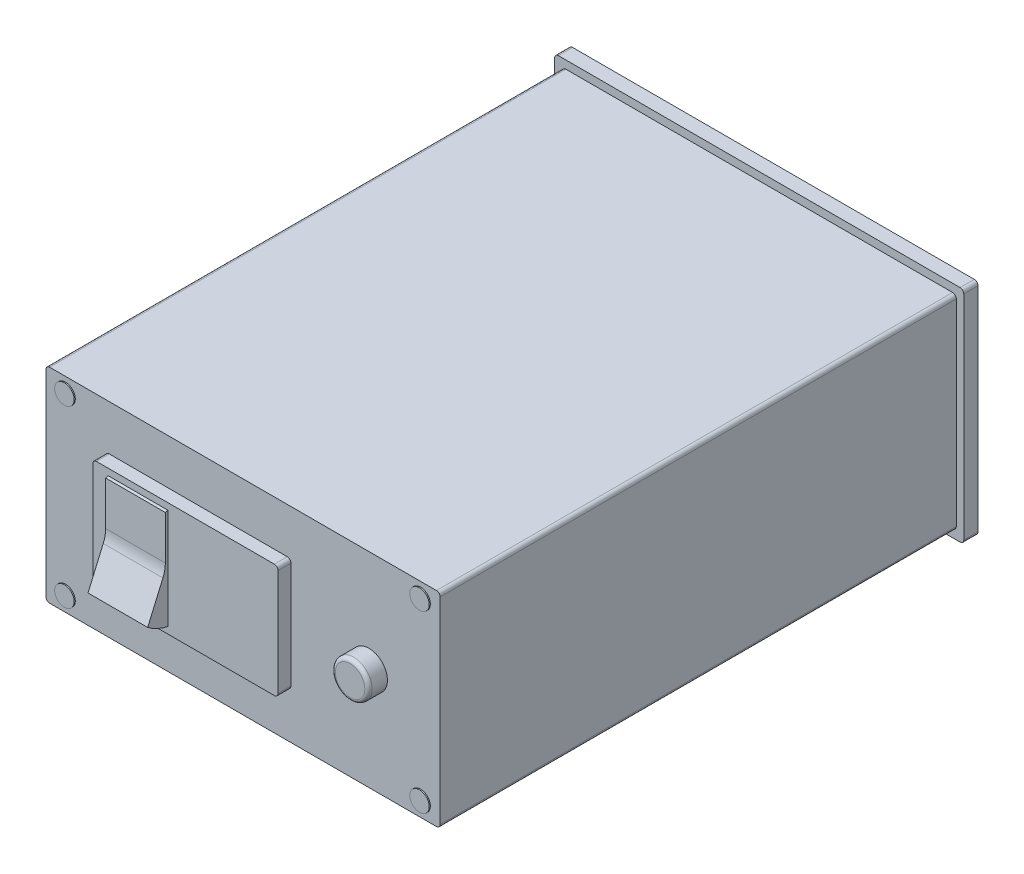
SolidWorks part; units mm, degrees
ref_plane "Front" through (0, 0, 0) normal (0, 0, 1) x (1, 0, 0)
ref_plane "Top" through (0, 0, 0) normal (0, 1, 0) x (1, 0, 0)
ref_plane "Right" through (0, 0, 0) normal (1, 0, 0) x (0, 0, -1)
sketch "Sketch1" plane through (0, 0, 0) normal (0, 0, 1) x (1, 0, 0)
  line L1 (-55.53, -29.925) -> (55.53, -29.925)
  line L2 (-55.53, -29.925) -> (-55.53, 29.925)
  line L3 (-55.53, 29.925) -> (55.53, 29.925)
  line L4 (55.53, -29.925) -> (55.53, 29.925)
  line L5 (-55.53, -29.925) -> (55.53, 29.925) construction
  line L6 (-55.53, 29.925) -> (55.53, -29.925) construction
  point P0 (0, 0)
  dimension "D1" = 59.85
  dimension "D2" = 111.06
extrude "Face" add sketch "Sketch1" along normal blind 3.86
fillet "Face Fillets" radius 1 4 edges at (-55.53, 29.925, 1.93) (-55.53, -29.925, 1.93) (55.53, -29.925, 1.93) (55.53, 29.925, 1.93)
sketch "Sketch2" plane through (0, 0, 0) normal (0, 0, 1) x (1, 0, 0)
  line L1 (-53.5, -27.75) -> (53.5, -27.75)
  line L2 (-53.5, -27.75) -> (-53.5, 27.75)
  line L3 (-53.5, 27.75) -> (53.5, 27.75)
  line L4 (53.5, -27.75) -> (53.5, 27.75)
  line L5 (-53.5, -27.75) -> (53.5, 27.75) construction
  line L6 (-53.5, 27.75) -> (53.5, -27.75) construction
  point P0 (0, 0)
  dimension "D1" = 107
  dimension "D2" = 55.5
extrude "Body" add sketch "Sketch2" along normal blind 144
sketch "Sketch3" plane through (0, -27.75, 0) normal (0, -1, 0) x (1, 0, 0)
  line L0 (-54.53, 3.86) -> (54.53, 3.86) construction
  line L1 (-36.625, 18.86) -> (36.625, 18.86) construction
  line L2 (-36.625, 18.86) -> (-36.625, 125.75) construction
  line L3 (-36.625, 125.75) -> (36.625, 125.75) construction
  line L4 (36.625, 18.86) -> (36.625, 125.75) construction
  line L5 (-36.625, 18.86) -> (36.625, 125.75) construction
  line L6 (-36.625, 125.75) -> (36.625, 18.86) construction
  line L7 (-53.5, 144) -> (53.5, 144) construction
  line L9 (-43, 119.375) -> (-30.25, 119.375)
  line L10 (-43, 119.375) -> (-43, 132.125)
  line L11 (-43, 132.125) -> (-30.25, 132.125)
  line L12 (-30.25, 119.375) -> (-30.25, 132.125)
  line L13 (-43, 119.375) -> (-30.25, 132.125) construction
  line L14 (-43, 132.125) -> (-30.25, 119.375) construction
  line L15 (30.25, 119.375) -> (43, 119.375)
  line L16 (30.25, 119.375) -> (30.25, 132.125)
  line L17 (30.25, 132.125) -> (43, 132.125)
  line L18 (43, 119.375) -> (43, 132.125)
  line L19 (30.25, 119.375) -> (43, 132.125) construction
  line L20 (30.25, 132.125) -> (43, 119.375) construction
  line L21 (30.25, 12.485) -> (43, 12.485)
  line L22 (30.25, 12.485) -> (30.25, 25.235)
  line L23 (30.25, 25.235) -> (43, 25.235)
  line L24 (43, 12.485) -> (43, 25.235)
  line L25 (30.25, 12.485) -> (43, 25.235) construction
  line L26 (30.25, 25.235) -> (43, 12.485) construction
  line L27 (-43, 12.485) -> (-30.25, 12.485)
  line L28 (-43, 12.485) -> (-43, 25.235)
  line L29 (-43, 25.235) -> (-30.25, 25.235)
  line L30 (-30.25, 12.485) -> (-30.25, 25.235)
  line L31 (-43, 12.485) -> (-30.25, 25.235) construction
  line L32 (-43, 25.235) -> (-30.25, 12.485) construction
  point P0 (0, 72.305)
  dimension "D1" = 15
  dimension "D2" = 18.25
  dimension "D3" = 73.25
  dimension "D4" = 12.75
extrude "Feet" add sketch "Sketch3" along normal blind 3.33 draft 25
fillet "Body Fillets" radius 1 4 edges at (53.5, 27.75, 73.93) (53.5, -27.75, 73.93) (-53.5, -27.75, 73.93) (-53.5, 27.75, 73.93)
sketch "Sketch4" plane through (0, 0, 144) normal (0, 0, 1) x (1, 0, 0)
  line L1 (53.5, -26.75) -> (53.5, 26.75) construction
  circle A0 centre (34.2, 0) radius 5
  dimension "D1" = 10
  dimension "D2" = 19.3
extrude "GND Bannana Port" add sketch "Sketch4" along normal blind 5.15
fillet "Fillet3" radius 1 1 edges at (39.2, 0, 149.15)
sketch "Sketch5" plane through (0, 0, 144) normal (0, 0, 1) x (1, 0, 0)
  line L1 (-37.3, -15.45) -> (13, -15.45)
  line L2 (-37.3, -15.45) -> (-37.3, 15.45)
  line L3 (-37.3, 15.45) -> (13, 15.45)
  line L4 (13, -15.45) -> (13, 15.45)
  line L5 (-37.3, -15.45) -> (13, 15.45) construction
  line L6 (-37.3, 15.45) -> (13, -15.45) construction
  line L7 (-53.5, 26.75) -> (-53.5, -26.75) construction
  point P0 (-12.15, 0)
  dimension "D1" = 50.3
  dimension "D2" = 30.9
  dimension "D3" = 16.2
extrude "Power Port" add sketch "Sketch5" along normal blind 3.5
fillet "Fillet4" radius 1 4 edges at (-37.3, 15.45, 145.75) (-37.3, -15.45, 145.75) (13, -15.45, 145.75) (13, 15.45, 145.75)
ref_plane "Switch Plane" through (-25, 0, 0) normal (1, 0, 0) x (0, 0, -1)
sketch "Sketch6" plane through (-25, 0, 0) normal (1, 0, 0) x (0, 0, -1)
  line L0 (-148.2, 13.5022) -> (-148.2, 1.6226)
  line L1 (-148.8582, -1.5551) -> (-153, -11.1243)
  line L2 (-144.5, 0) -> (-148.3663, 0) construction
  line L3 (-147.5, -14.45) -> (-147.5, 14.45) construction
  circle A0 centre (-144.5, 0) radius 14 construction
  arc A1 (-148.2, 1.6226) -> (-148.8582, -1.5551) centre (-156.2, 1.6226) cw
  arc A2 (-148.2, 13.5022) -> (-153, -11.1243) centre (-144.5, 0) cw
  dimension "D1" = 28
  dimension "D2" = 8
  dimension "D3" = 5.5
  dimension "D4" = 0.7
  dimension "D5" = 3
extrude "Boss-Extrude6" add sketch "Sketch6" along normal mid plane 16.2
sketch "Sketch7" plane through (0, 0, 0) normal (0, 0, -1) x (-1, 0, 0)
  line L0 (-55.53, -28.925) -> (-55.53, 28.925) construction
  line L1 (54.53, -29.925) -> (-54.53, -29.925) construction
  circle A0 centre (-34.53, -2.925) radius 6.5
  dimension "D1" = 13
  dimension "D2" = 21
  dimension "D3" = 27
extrude "Boss-Extrude7" add sketch "Sketch7" along normal mid plane 4.7
sketch "Sketch8" plane through (0, 0, 144) normal (0, 0, 1) x (1, 0, 0)
  line L0 (-53.5, 26.75) -> (-53.5, -26.75) construction
  line L1 (52.5, 27.75) -> (-52.5, 27.75) construction
  circle A0 centre (-48.2, 23.75) radius 2.65
  dimension "D1" = 5.3
  dimension "D2" = 5.3
  dimension "D3" = 4
extrude "Boss-Extrude8" add sketch "Sketch8" along normal mid plane 0.6
mirror "Mirror1" about plane through (0, 0, 0) normal (1, 0, 0) of "Boss-Extrude8"
mirror "Mirror2" about plane through (0, 0, 0) normal (0, 1, 0) of "Mirror1"
ref_plane "Plane2" through (0, -19, 0) normal (0, 1, 0) x (1, 0, 0)
sketch "Aligner Guide" plane through (0, -19, 0) normal (0, 1, 0) x (1, 0, 0)
  line L0 (-27.6997, 0.4) -> (25.0059, 0.4)
  line L1 (54.53, 0) -> (-54.53, 0) construction
  line L2 (53.9, -10.1769) -> (53.9, -139.7462)
  line L3 (-53.9, -10.1769) -> (-53.9, -139.7462)
  line L4 (-29.1637, -144.4) -> (31.0456, -144.4)
  line L5 (52.5, -144) -> (-52.5, -144) construction
  line L6 (-53.5, -144) -> (-53.5, -3.86) construction
  line L7 (53.5, -3.86) -> (53.5, -144) construction
  dimension "D1" = 0.4
  dimension "D2" = 0.4
  dimension "D3" = 0.4
  dimension "D4" = 0.4
